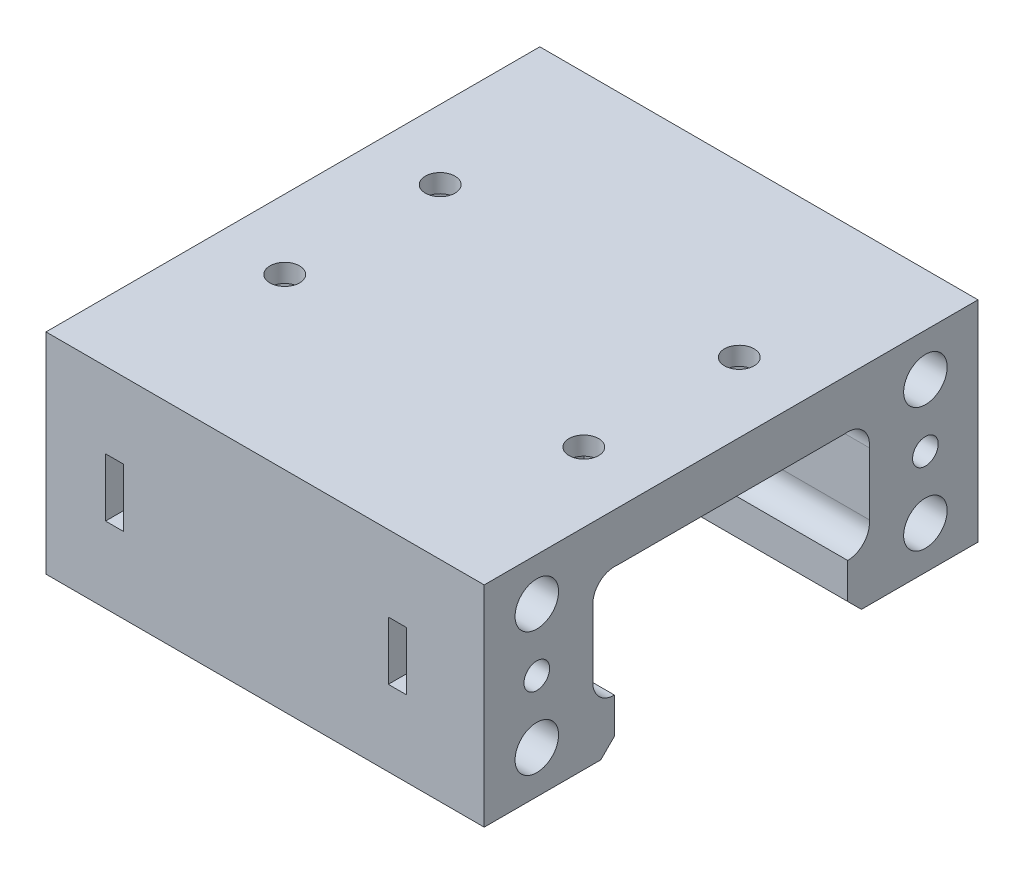
SolidWorks part; units mm, degrees
ref_plane "Front Plane" through (0, 0, 0) normal (0, 0, 1) x (1, 0, 0)
ref_plane "Top Plane" through (0, 0, 0) normal (0, 1, 0) x (1, 0, 0)
ref_plane "Right Plane" through (0, 0, 0) normal (1, 0, 0) x (0, 0, -1)
sketch "Sketch1" plane through (0, 0, 0) normal (1, 0, 0) x (0, 0, -1)
  line L0 (0, 0) -> (30, 0)
  line L1 (0, 0) -> (0, 5)
  line L2 (0, 5) -> (2.7781, 7.7781)
  line L3 (2.7781, 7.7781) -> (2.7781, 14.2781)
  line L4 (2.7781, 14.2781) -> (0, 14.2781) construction
  line L5 (0, 14.2781) -> (0, 23) construction
  line L6 (0, 23) -> (30, 23) construction
  line L12 (15, 0) -> (15, 23) construction
  line L13 (27.2219, 23) -> (2.7781, 23)
  line L14 (0, 20.2219) -> (0, 17.0562)
  line L15 (30, 14.2781) -> (30, 23) construction
  line L16 (27.2219, 14.2781) -> (30, 14.2781) construction
  line L17 (30, 20.2219) -> (30, 17.0562)
  line L18 (27.2219, 7.7781) -> (27.2219, 14.2781)
  line L19 (30, 5) -> (27.2219, 7.7781)
  line L20 (30, 0) -> (30, 5)
  arc A0 (2.7781, 14.2781) -> (0, 17.0562) centre (0, 14.2781) ccw
  arc A1 (0, 20.2219) -> (2.7781, 23) centre (0, 23) ccw
  arc A2 (30, 20.2219) -> (27.2219, 23) centre (30, 23) cw
  arc A3 (27.2219, 14.2781) -> (30, 17.0562) centre (30, 14.2781) cw
  dimension "D1" = 5.5563
  dimension "D2" = 15
  dimension "D3" = 23
  dimension "D4" = 45
  dimension "D5" = 6.5
  dimension "D6" = 5
sketch "Sketch2" plane through (0, 0, 0) normal (1, 0, 0) x (0, 0, -1)
  line L0 (-10, 26.6391) -> (-10, 32.1391) construction
  line L1 (15, 23) -> (15, -0.4684) construction
  line L2 (-10, 10.6391) -> (-10, 5.1391) construction
  line L3 (0, 25.7781) -> (30, 25.7781)
  line L4 (0, 11.5) -> (0, 6.9068)
  line L5 (0, 6.9068) -> (-1.7678, 5.1391)
  line L6 (-1.7678, 5.1391) -> (-16.7678, 5.1391)
  line L7 (-16.7678, 5.1391) -> (-16.7678, 32.1391)
  line L8 (-10, 26.6391) -> (0, 23) construction
  line L9 (0, 23) -> (0, 14.2781) construction
  line L10 (0, 14.2781) -> (-10, 10.6391) construction
  line L11 (-10, 10.6391) -> (-10, 26.6391) construction
  line L12 (0, 18.6391) -> (-10, 18.6391) construction
  line L13 (-16.7678, 32.1391) -> (46.7678, 32.1391)
  line L14 (15, 32.1391) -> (15, 25.7781) construction
  line L15 (-2.7781, 14.2781) -> (-2.7781, 23)
  line L16 (0, 5) -> (2.7781, 7.7781) construction
  line L17 (15, 0) -> (15, 23) construction
  line L18 (30, 18.6391) -> (40, 18.6391) construction
  line L19 (40, 10.6391) -> (40, 26.6391) construction
  line L20 (30, 14.2781) -> (40, 10.6391) construction
  line L21 (30, 23) -> (30, 14.2781) construction
  line L22 (40, 26.6391) -> (30, 23) construction
  line L23 (40, 10.6391) -> (40, 5.1391) construction
  line L24 (40, 26.6391) -> (40, 32.1391) construction
  line L25 (32.7781, 14.2781) -> (32.7781, 23)
  line L26 (46.7678, 5.1391) -> (46.7678, 32.1391)
  line L27 (31.7678, 5.1391) -> (46.7678, 5.1391)
  line L28 (30, 6.9068) -> (31.7678, 5.1391)
  line L29 (30, 11.5) -> (30, 6.9068)
  arc A0 (0, 25.7781) -> (-2.7781, 23) centre (0, 23) ccw
  arc A1 (-2.7781, 14.2781) -> (0, 11.5) centre (0, 14.2781) ccw
  arc A2 (2.7781, 14.2781) -> (0, 17.0562) centre (0, 14.2781) ccw construction
  circle A3 centre (-10, 26.6391) radius 2.7781
  circle A4 centre (-10, 10.6391) radius 2.7781
  circle A5 centre (40, 10.6391) radius 2.7781
  circle A6 centre (40, 26.6391) radius 2.7781
  arc A7 (32.7781, 14.2781) -> (30, 11.5) centre (30, 14.2781) cw
  arc A8 (30, 25.7781) -> (32.7781, 23) centre (30, 23) cw
  dimension "D1" = 10
  dimension "D2" = 16
  dimension "D3" = 15
  dimension "D4" = 27
  dimension "D5" = 2.5
extrude "Boss-Extrude2" add sketch "Sketch2" along normal blind 56.3836
sketch "Sketch3" plane through (56.3836, 0, 0) normal (1, 0, 0) x (0, 0, -1)
  line L0 (-10, 26.6391) -> (-10, 10.6391) construction
  line L1 (15, 20.921) -> (15, 13.7492) construction
  line L2 (15, 200023) -> (15, -200000.4684) construction
  line L3 (-10, 18.6391) -> (15, 18.6391) construction
  circle A0 centre (-10, 18.6391) radius 1.651
  circle A1 centre (40, 18.6391) radius 1.651
  dimension "D1" = 3.302
extrude "Cut-Extrude1" cut sketch "Sketch3" against normal blind 22.1668
ref_plane "Plane1" through (14.3012, 0, 0) normal (1, 0, 0) x (0, 0, -1)
ref_plane "Plane2" through (0, 18.6391, 0) normal (0, -1, 0) x (0, 0, -1)
ref_axis "Axis1" through (-60.3203, 18.6391, 10) along (1, 0, 0)
ref_axis "Axis2" through (56.3836, 18.6391, -40) along (1, 0, 0)
sketch "Sketch4" plane through (0, 18.6391, 0) normal (0, -1, 0) x (0, 0, -1)
  line L0 (-16.7678, 56.3836) -> (-16.7678, 0) construction
  line L1 (-16.7678, 46.3836) -> (-6, 46.3836)
  line L2 (-16.7678, 46.3836) -> (-16.7678, 44.0436)
  line L3 (-16.7678, 44.0436) -> (-6, 44.0436)
  line L4 (-6, 46.3836) -> (-6, 44.0436)
  line L5 (46.7678, 56.3836) -> (46.7678, 0) construction
  line L6 (46.7678, 46.3836) -> (36, 46.3836)
  line L7 (46.7678, 46.3836) -> (46.7678, 44.0436)
  line L8 (46.7678, 44.0436) -> (36, 44.0436)
  line L9 (36, 46.3836) -> (36, 44.0436)
  line L10 (-16.7678, 56.3836) -> (-1.7678, 56.3836) construction
  line L11 (-16.7678, 7.66) -> (-6, 7.66)
  line L12 (-16.7678, 7.66) -> (-16.7678, 10)
  line L13 (-16.7678, 10) -> (-6, 10)
  line L14 (-6, 7.66) -> (-6, 10)
  line L15 (36, 7.66) -> (46.7678, 7.66)
  line L16 (36, 7.66) -> (36, 10)
  line L17 (36, 10) -> (46.7678, 10)
  line L18 (46.7678, 7.66) -> (46.7678, 10)
  line L19 (-16.7678, 0) -> (-1.7678, 0) construction
  line L20 (-10, -60.3203) -> (-10, 103.1706) construction
  dimension "D1" = 10
  dimension "D2" = 10
  dimension "D3" = 4
  dimension "D4" = 2.34
extrude "Cut-Extrude2" cut sketch "Sketch4" against normal mid plane 7.5
sketch "Sketch5" plane through (56.3836, 0, 0) normal (1, 0, 0) x (0, 0, -1)
  circle A0 centre (-10, 26.6391) radius 2.8
  circle A1 centre (0, 23) radius 2.8
  circle A2 centre (-10, 10.6391) radius 2.8
  circle A3 centre (40, 26.6391) radius 2.8
  circle A4 centre (40, 10.6391) radius 2.8
  circle A5 centre (30, 23) radius 2.8
  circle A6 centre (0, 14.2781) radius 2.8
  circle A7 centre (30, 14.2781) radius 2.8
  arc A8 (0, 25.7781) -> (-2.7781, 23) centre (0, 23) ccw construction
  arc A9 (-2.7781, 14.2781) -> (0, 11.5) centre (0, 14.2781) ccw construction
  arc A10 (30, 11.5) -> (32.7781, 14.2781) centre (30, 14.2781) ccw construction
  arc A11 (32.7781, 23) -> (30, 25.7781) centre (30, 23) ccw construction
  dimension "D1" = 5.6
extrude "Cut-Extrude3" cut sketch "Sketch5" against normal through all
ref_plane "Plane3" through (28.1918, 0, 0) normal (-1, 0, 0) x (0, 0, 1)
mirror "Mirror1" about plane through (28.1918, 0, 0) normal (-1, 0, 0) of "Cut-Extrude1"
sketch "Sketch6" plane through (0, 25.7781, 0) normal (0, -1, 0) x (1, 0, 0)
  line L0 (0, -0.3493) -> (56.3836, -29.6507) construction
  line L1 (56.3836, -0.3493) -> (0, -29.6507) construction
  line L3 (47.4344, -25) -> (8.9491, -25) construction
  line L4 (47.4344, -25) -> (47.4344, -5) construction
  line L5 (47.4344, -5) -> (8.9491, -5) construction
  line L6 (8.9491, -25) -> (8.9491, -5) construction
  line L7 (47.4344, -25) -> (8.9491, -5) construction
  line L8 (47.4344, -5) -> (8.9491, -25) construction
  circle A0 centre (8.9491, -5) radius 1.905
  circle A1 centre (47.4344, -5) radius 1.905
  circle A2 centre (47.4344, -25) radius 1.905
  circle A3 centre (8.9491, -25) radius 1.905
  point P8 (28.1918, -15)
  dimension "D1" = 3.81
  dimension "D2" = 20
extrude "Cut-Extrude4" cut sketch "Sketch6" against normal through all
sketch "Sketch7" plane through (0, 25.7781, 0) normal (0, -1, 0) x (-1, 0, 0)
  line L1 (-12.1669, 27.282) -> (-12.5343, 23.3543)
  line L2 (-12.5343, 23.3543) -> (-9.3165, 21.0723)
  line L3 (-9.3165, 21.0723) -> (-5.7314, 22.718)
  line L4 (-5.7314, 22.718) -> (-5.364, 26.6457)
  line L5 (-5.364, 26.6457) -> (-8.5818, 28.9277)
  line L6 (-8.5818, 28.9277) -> (-12.1669, 27.282)
  line L7 (-12.4658, 6.7874) -> (-12.2554, 2.8482)
  line L8 (-12.2554, 2.8482) -> (-8.7387, 1.0608)
  line L9 (-8.7387, 1.0608) -> (-5.4325, 3.2126)
  line L10 (-5.4325, 3.2126) -> (-5.6429, 7.1518)
  line L11 (-5.6429, 7.1518) -> (-9.1596, 8.9392)
  line L12 (-9.1596, 8.9392) -> (-12.4658, 6.7874)
  line L13 (-44.6712, 7.8153) -> (-48.4909, 8.8007)
  line L14 (-48.4909, 8.8007) -> (-51.2542, 5.9854)
  line L15 (-51.2542, 5.9854) -> (-50.1977, 2.1847)
  line L16 (-50.1977, 2.1847) -> (-46.3779, 1.1993)
  line L17 (-46.3779, 1.1993) -> (-43.6147, 4.0146)
  line L18 (-43.6147, 4.0146) -> (-44.6712, 7.8153)
  line L19 (-43.8964, 26.7447) -> (-47.1764, 28.9364)
  line L20 (-47.1764, 28.9364) -> (-50.7144, 27.1916)
  line L21 (-50.7144, 27.1916) -> (-50.9724, 23.2553)
  line L22 (-50.9724, 23.2553) -> (-47.6924, 21.0636)
  line L23 (-47.6924, 21.0636) -> (-44.1544, 22.8084)
  line L24 (-44.1544, 22.8084) -> (-43.8964, 26.7447)
  circle A0 centre (-8.9491, 25) radius 3.4163 construction
  circle A1 centre (-8.9491, 5) radius 3.4163 construction
  circle A2 centre (-47.4344, 5) radius 3.4163 construction
  circle A3 centre (-47.4344, 25) radius 3.4163 construction
  dimension "D1" = 6.8326
extrude "Cut-Extrude5" cut sketch "Sketch7" against normal blind 4
